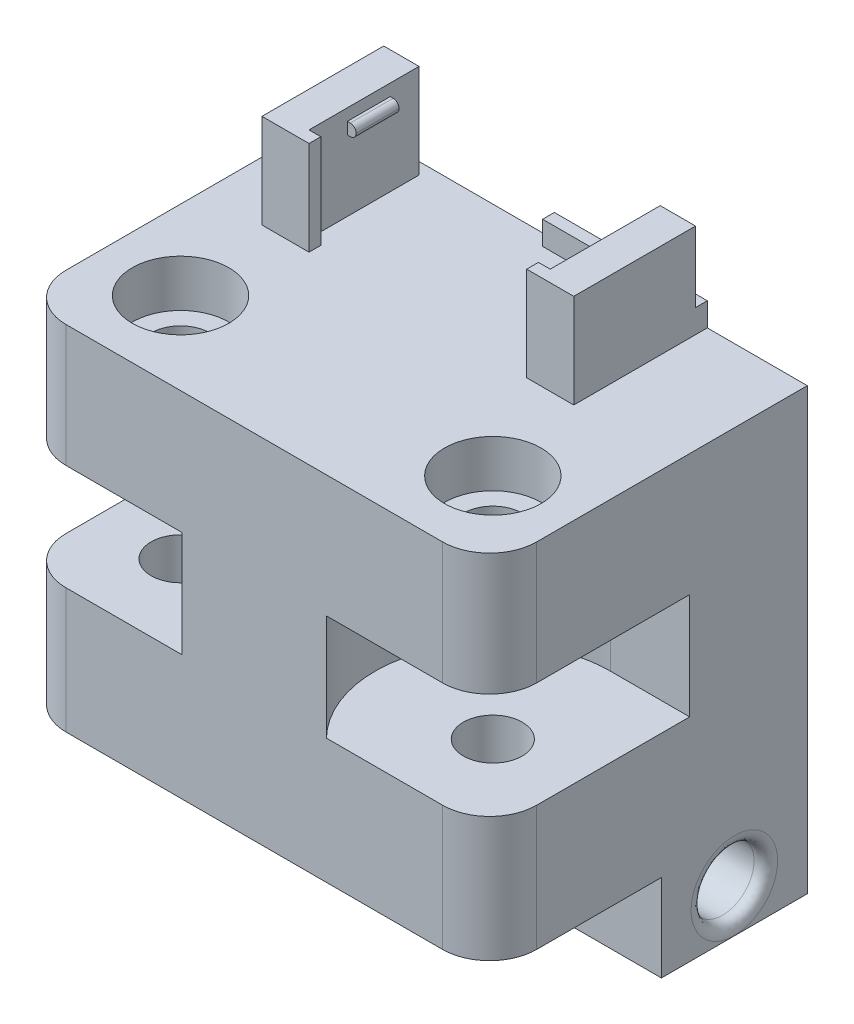
SolidWorks part; units mm, degrees
ref_plane "Front Plane" through (0, 0, 0) normal (0, 0, 1) x (1, 0, 0)
ref_plane "Top Plane" through (0, 0, 0) normal (0, 1, 0) x (1, 0, 0)
ref_plane "Right Plane" through (0, 0, 0) normal (1, 0, 0) x (0, 0, -1)
sketch "Sketch1" plane through (0, 0, 0) normal (0, 1, 0) x (1, 0, 0)
  line L1 (-22.8462, -9.1868) -> (17.1538, -9.1868)
  line L2 (-22.8462, -9.1868) -> (-22.8462, 17.8132)
  line L3 (-22.8462, 17.8132) -> (17.1538, 17.8132)
  line L4 (17.1538, -9.1868) -> (17.1538, 17.8132)
  dimension "D1" = 27
  dimension "D2" = 40
extrude "Boss-Extrude1" add sketch "Sketch1" along normal blind 30
sketch "Sketch2" plane through (0, 0, -17.8132) normal (0, 0, -1) x (-1, 0, 0)
  line L0 (2.8462, 30) -> (2.8462, 0) construction
  line L1 (-8.0864, 4) -> (-0.2064, 4)
  line L2 (-0.2064, 4) -> (-0.2064, 7)
  line L3 (-0.2064, 7) -> (-2.8664, 7)
  line L4 (-2.8664, 7) -> (-2.8664, 8.0087)
  line L5 (-2.8664, 8.0087) -> (-0.2538, 10.6287)
  line L6 (-0.2538, 10.6287) -> (5.9462, 10.6287)
  line L7 (-17.1538, 30) -> (22.8462, 30) construction
  line L8 (-17.1538, 0) -> (22.8462, 0) construction
  line L9 (-8.0864, 4) -> (-8.0864, 26)
  line L10 (-8.0864, 26) -> (-0.2064, 26)
  line L11 (-0.2064, 26) -> (-0.2064, 23)
  line L12 (-0.2064, 23) -> (-2.8664, 23)
  line L13 (-2.8664, 23) -> (-2.8664, 21.9913)
  line L14 (-2.8664, 21.9913) -> (-0.2464, 19.3787)
  line L15 (-0.2464, 19.3787) -> (5.9536, 19.3787)
  line L16 (-17.1538, 15) -> (22.8462, 15) construction
  line L17 (-17.1538, 30) -> (-17.1538, 0) construction
  line L18 (22.8462, 30) -> (22.8462, 0) construction
  line L19 (5.9387, 19.3787) -> (-0.2613, 19.3787)
  line L20 (8.5587, 21.9913) -> (5.9387, 19.3787)
  line L21 (8.5587, 23) -> (8.5587, 21.9913)
  line L22 (5.8987, 23) -> (8.5587, 23)
  line L23 (5.8987, 26) -> (5.8987, 23)
  line L24 (13.7787, 26) -> (5.8987, 26)
  line L25 (13.7787, 4) -> (13.7787, 26)
  line L26 (8.5587, 8.0087) -> (5.9462, 10.6287)
  line L27 (8.5587, 7) -> (8.5587, 8.0087)
  line L28 (5.8987, 7) -> (8.5587, 7)
  line L29 (5.8987, 4) -> (5.8987, 7)
  line L30 (13.7787, 4) -> (5.8987, 4)
  point P26 (-8.0864, 15)
  point P27 (2.8462, 15)
  point P37 (2.8462, 10.6287)
  dimension "D1" = 6.2
  dimension "D2" = 2.62
  dimension "D3" = 3.7
  dimension "D4" = 8.75
  dimension "D5" = 7.88
  dimension "D6" = 22
  dimension "D7" = 5.22
  dimension "D8" = 3
  dimension "D9" = 90
extrude "Cut-Extrude1" cut sketch "Sketch2" against normal blind 10 contours L30 L25 L24 L23 L22 L21 L20 L15 L14 L13 L12 L11 L10 L9 L1 L2 L3 L4 L5 L6 L26 L27 L28 L29 region at (-2.8462, 15.0011, -17.8132)
sketch "Sketch3" plane through (0, 0, 0) normal (0, -1, 0) x (1, 0, 0)
  line L0 (-22.8462, 9.1868) -> (17.1538, 9.1868) construction
  line L1 (17.1538, 9.1868) -> (17.1538, -17.8132) construction
  line L2 (-2.8462, 9.1868) -> (-2.8462, -17.8132) construction
  line L3 (17.1538, -17.8132) -> (-22.8462, -17.8132) construction
  circle A0 centre (10.4238, 2.1868) radius 2.5
  circle A2 centre (-16.1162, 2.1868) radius 2.5
  dimension "D1" = 5
  dimension "D3" = 7
  dimension "D4" = 6.73
extrude "Cut-Extrude2" cut sketch "Sketch3" against normal blind 30
sketch "Sketch8" plane through (0, 0, 0) normal (0, -1, 0) x (1, 0, 0)
  line L0 (3.2824, 9.1868) -> (17.1538, 9.1868)
  line L1 (-22.8462, 9.1868) -> (17.1538, 9.1868) construction
  line L2 (17.1538, 9.1868) -> (17.1538, -7.8132)
  line L3 (17.1538, 9.1868) -> (17.1538, -17.8132) construction
  line L4 (17.1538, -7.8132) -> (10.4238, -7.8132)
  line L6 (-2.8462, -17.8132) -> (-2.8462, 9.1868) construction
  line L7 (17.1538, -17.8132) -> (-22.8462, -17.8132) construction
  line L8 (-22.8462, -7.8132) -> (-16.1162, -7.8132)
  line L9 (-22.8462, 9.1868) -> (-22.8462, -7.8132)
  line L10 (-8.9747, 9.1868) -> (-22.8462, 9.1868)
  arc A0 (10.4238, -7.8132) -> (3.2824, 9.1868) centre (10.4238, 2.1868) cw
  arc A1 (-16.1162, -7.8132) -> (-8.9747, 9.1868) centre (-16.1162, 2.1868) ccw
  circle M6 centre (10.4238, 2.1868) radius 2.5
  circle M7 centre (-16.1162, 2.1868) radius 2.5
  line M8 (-22.8462, 9.1868) -> (-22.8462, -17.8132)
  line M10 (17.1538, -17.8132) -> (17.1538, 9.1868)
  line M11 (17.1538, 9.1868) -> (-22.8462, 9.1868)
  dimension "D1" = 10
extrude "Cut-Extrude5" cut sketch "Sketch8" against normal blind 9 from offset 10.62 contours A0 L4 M10 M11 M6 | M6 | L8 A1 M11 M8 M7 | M7 region at (10.2181, 0, 8.9483) region at (-7.1165, 0, -1.5938) region at (10.4238, 0, 2.1868) region at (-16.1162, 0, 2.1868) offset against normal yes
sketch "Sketch10" plane through (8.0864, 0, 0) normal (-1, 0, 0) x (0, 0, 1)
  line L0 (-17.8132, 30) -> (-17.8132, 0) construction
  line L1 (-17.8132, 19.62) -> (2.1868, 19.62)
  line L2 (-17.8132, 19.62) -> (-17.8132, 10.62)
  line L3 (-17.8132, 10.62) -> (2.1868, 10.62)
  line L4 (2.1868, 19.62) -> (2.1868, 10.62)
  line L6 (-7.8132, 19.62) -> (9.1868, 19.62) construction
  dimension "D1" = 20
extrude "Cut-Extrude7" cut sketch "Sketch10" along normal blind 6.8
sketch "Sketch12" plane through (-13.7787, 0, 0) normal (1, 0, 0) x (0, 0, -1)
  line L3 (17.8132, 10.62) -> (-2.1868, 10.62)
  line L6 (-2.1868, 10.62) -> (-2.1868, 19.62)
  line L7 (7.8132, 19.62) -> (-9.1868, 19.62) construction
  line L8 (-2.1868, 19.62) -> (17.8132, 19.62)
  line L9 (17.8132, 30) -> (17.8132, 0) construction
  line L10 (17.8132, 19.62) -> (17.8132, 10.62)
extrude "Cut-Extrude10" cut sketch "Sketch12" along normal blind 6.8
fillet "Fillet1" radius 4 4 edges at (17.1538, 5.31, 9.1868) (17.1538, 24.81, 9.1868) (-22.8462, 5.31, 9.1868) (-22.8462, 24.81, 9.1868)
sketch "Sketch13" plane through (17.1538, 0, 0) normal (1, 0, 0) x (0, 0, -1)
  line L0 (-5.1868, 0) -> (17.8132, 0) construction
  line L1 (17.8132, 30) -> (17.8132, 0) construction
  line L3 (17.8132, 0) -> (5.4132, 0)
  line L4 (17.8132, 0) -> (17.8132, -7.4)
  line L5 (17.8132, -7.4) -> (5.4132, -7.4)
  line L6 (5.4132, 0) -> (5.4132, -7.4)
  circle A0 centre (11.6132, -3.7) radius 2.675
  dimension "D1" = 6.2
  dimension "D2" = 3.7
  dimension "D3" = 5.35
  dimension "D4" = 12.4
  dimension "D5" = 7.4
extrude "Boss-Extrude2" add sketch "Sketch13" against normal up to surface (40 mm away) up to face at (-22.8462, 15.06, -3.8132)
sketch "Sketch14" plane through (0, 0, -5.4132) normal (0, 0, 1) x (1, 0, 0)
  line L0 (-22.8462, -7.4) -> (17.1538, -7.4) construction
  line L1 (-12.8462, -7.4) -> (7.1538, -7.4)
  line L2 (-12.8462, -7.4) -> (-12.8462, 0)
  line L3 (-12.8462, 0) -> (7.1538, 0)
  line L4 (7.1538, -7.4) -> (7.1538, 0)
  line L5 (-18.8462, 0) -> (13.1538, 0) construction
  line L7 (17.1538, 0) -> (17.1538, -7.4) construction
  dimension "D1" = 20
  dimension "D2" = 10
extrude "Cut-Extrude11" cut sketch "Sketch14" against normal up to next
sketch "Sketch15" plane through (0, 30, 0) normal (0, 1, 0) x (1, 0, 0)
  line L0 (-2.8462, 17.8132) -> (-2.8462, -9.1868) construction
  line L13 (17.1538, 17.8132) -> (-22.8462, 17.8132) construction
  line L14 (-18.8462, -9.1868) -> (13.1538, -9.1868) construction
  circle A4 centre (-16.1162, -2.1868) radius 4.1
  circle A5 centre (10.4238, -2.1868) radius 4.1
  dimension "D1" = 8.2
extrude "Cut-Extrude12" cut sketch "Sketch15" against normal blind 4
sketch "Sketch16" plane through (0, 0, 0) normal (0, -1, 0) x (1, 0, 0)
  line L1 (-13.749, -1.9132) -> (-11.3819, 2.1868)
  line L2 (-11.3819, 2.1868) -> (-13.749, 6.2868)
  line L3 (-13.749, 6.2868) -> (-18.4833, 6.2868)
  line L4 (-18.4833, 6.2868) -> (-20.8504, 2.1868)
  line L5 (-20.8504, 2.1868) -> (-18.4833, -1.9132)
  line L6 (-18.4833, -1.9132) -> (-13.749, -1.9132)
  line L7 (12.791, -1.9132) -> (15.1581, 2.1868)
  line L8 (15.1581, 2.1868) -> (12.791, 6.2868)
  line L9 (12.791, 6.2868) -> (8.0567, 6.2868)
  line L10 (8.0567, 6.2868) -> (5.6896, 2.1868)
  line L11 (5.6896, 2.1868) -> (8.0567, -1.9132)
  line L12 (8.0567, -1.9132) -> (12.791, -1.9132)
  circle A0 centre (10.4238, 2.1868) radius 2.5 construction
  circle A1 centre (-16.1162, 2.1868) radius 2.5 construction
  circle A2 centre (10.4238, 2.1868) radius 2.5
  circle A3 centre (-16.1162, 2.1868) radius 2.5
  circle A4 centre (-16.1162, 2.1868) radius 4.1 construction
  circle A5 centre (10.4238, 2.1868) radius 4.1 construction
  dimension "D1" = 8.2
  dimension "D2" = 8.2
extrude "Cut-Extrude13" cut sketch "Sketch16" against normal blind 4
sketch "Sketch17" plane through (0, 30, 0) normal (0, 1, 0) x (1, 0, 0)
  line L1 (8.6538, 16.8132) -> (5.6538, 16.8132)
  line L2 (8.6538, 16.8132) -> (8.6538, 7.4632)
  line L3 (8.6538, 7.4632) -> (5.6538, 7.4632)
  line L4 (-18.8462, -9.1868) -> (13.1538, -9.1868)
  line L5 (17.1538, -5.1868) -> (17.1538, 17.8132)
  line L6 (17.1538, 17.8132) -> (-22.8462, 17.8132)
  line L7 (-22.8462, 17.8132) -> (-22.8462, -5.1868)
  line L8 (-18.8462, -9.1868) -> (13.1538, -9.1868)
  line L9 (17.1538, -5.1868) -> (17.1538, 17.8132)
  line L10 (17.1538, 17.8132) -> (-22.8462, 17.8132)
  line L11 (-22.8462, 17.8132) -> (-22.8462, -5.1868)
  line L12 (5.6538, 16.8132) -> (5.6538, 7.4632)
  line L13 (-14.8462, 16.8132) -> (-17.8462, 16.8132)
  line L14 (-14.8462, 16.8132) -> (-14.8462, 7.4632)
  line L15 (-14.8462, 7.4632) -> (-17.8462, 7.4632)
  line L16 (-17.8462, 16.8132) -> (-17.8462, 7.4632)
  line L17 (8.6538, 7.4632) -> (4.6538, 7.4632)
  line L18 (8.6538, 7.4632) -> (8.6538, 6.4632)
  line L19 (8.6538, 6.4632) -> (4.6538, 6.4632)
  line L20 (4.6538, 7.4632) -> (4.6538, 6.4632)
  line L21 (-17.8462, 7.4632) -> (-13.8462, 7.4632)
  line L22 (-17.8462, 7.4632) -> (-17.8462, 6.4632)
  line L23 (-17.8462, 6.4632) -> (-13.8462, 6.4632)
  line L24 (-13.8462, 7.4632) -> (-13.8462, 6.4632)
  arc A2 (13.1538, -9.1868) -> (17.1538, -5.1868) centre (13.1538, -5.1868) ccw
  arc A3 (-22.8462, -5.1868) -> (-18.8462, -9.1868) centre (-18.8462, -5.1868) ccw
  arc A4 (13.1538, -9.1868) -> (17.1538, -5.1868) centre (13.1538, -5.1868) ccw
  arc A5 (-22.8462, -5.1868) -> (-18.8462, -9.1868) centre (-18.8462, -5.1868) ccw
  line M30 (17.1538, 17.8132) -> (-22.8462, 17.8132)
  dimension "D2" = 9.35
  dimension "D3" = 3
  dimension "D4" = 3
  dimension "D5" = 20.5
  dimension "D6" = 5
  dimension "D7" = 1
  dimension "D8" = 1
  dimension "D9" = 4
  dimension "D10" = 1
  dimension "D11" = 1
  dimension "D1" = 0
extrude "Boss-Extrude3" add sketch "Sketch17" along normal blind 8 contours L12 L3 L2 M30 | L10 L16 L15 L14 | L24 L21 L15 L22 L23 | L17 L20 L19 L18 L3 region at (7.1538, 30, -12.1382) region at (6.6538, 30, -6.9632) region at (-16.3462, 30, -12.1382) region at (-15.8462, 30, -6.9632)
sketch "Sketch20" plane through (0, 38, 0) normal (0, 1, 0) x (1, 0, 0)
  line L0 (5.6538, 16.8132) -> (5.6538, 7.4632) construction
  line L1 (5.6538, 14.3623) -> (4.9038, 14.3623)
  line L2 (5.6538, 14.3623) -> (5.6538, 10.716)
  line L3 (5.6538, 10.716) -> (4.9038, 10.716)
  line L4 (4.9038, 14.3623) -> (4.9038, 10.716)
  line L5 (-14.8462, 16.8132) -> (-14.8462, 7.4632) construction
  line L6 (-14.8462, 14.3623) -> (-14.0962, 14.3623)
  line L7 (-14.8462, 14.3623) -> (-14.8462, 10.716)
  line L8 (-14.8462, 10.716) -> (-14.0962, 10.716)
  line L9 (-14.0962, 14.3623) -> (-14.0962, 10.716)
  dimension "D1" = 0.75
  dimension "D2" = 0.75
extrude "Boss-Extrude4" add sketch "Sketch20" along normal blind 1 from offset 2 offset against normal yes
fillet "Fillet2" radius 0.5 4 edges at (-14.0962, 36, -12.5391) (4.9038, 36, -12.5391) (-14.0962, 37, -12.5391) (4.9038, 37, -12.5391)
sketch "Sketch22" plane through (0, 0, -17.8132) normal (0, 0, -1) x (-1, 0, 0)
  line L1 (-8.6538, 32) -> (4.3462, 32)
  line L2 (-8.6538, 32) -> (-8.6538, 30)
  line L3 (-8.6538, 30) -> (4.3462, 30)
  line L4 (4.3462, 32) -> (4.3462, 30)
  line L7 (-5.6538, 38) -> (-5.6538, 30) construction
  line L8 (-5.6538, 38) -> (-5.6538, 30)
  line L9 (-17.1538, 30) -> (22.8462, 30) construction
  line L11 (-8.6538, 38) -> (-8.6538, 30) construction
  dimension "D1" = 2
  dimension "D2" = 13
extrude "Boss-Extrude6" add sketch "Sketch22" along normal blind 1 from surface contours L8 L1 L2 L3 | L1 L8 L3 L4 region at (7.1538, 31, -17.8132) region at (0.6538, 31, -17.8132) starting at face at (7.1538, 34, -16.8132)
fillet "Fillet3" radius 1 2 edges at (-22.8462, -3.7, -14.2882) (17.1538, -3.7, -14.2882) conic rho 0.5
